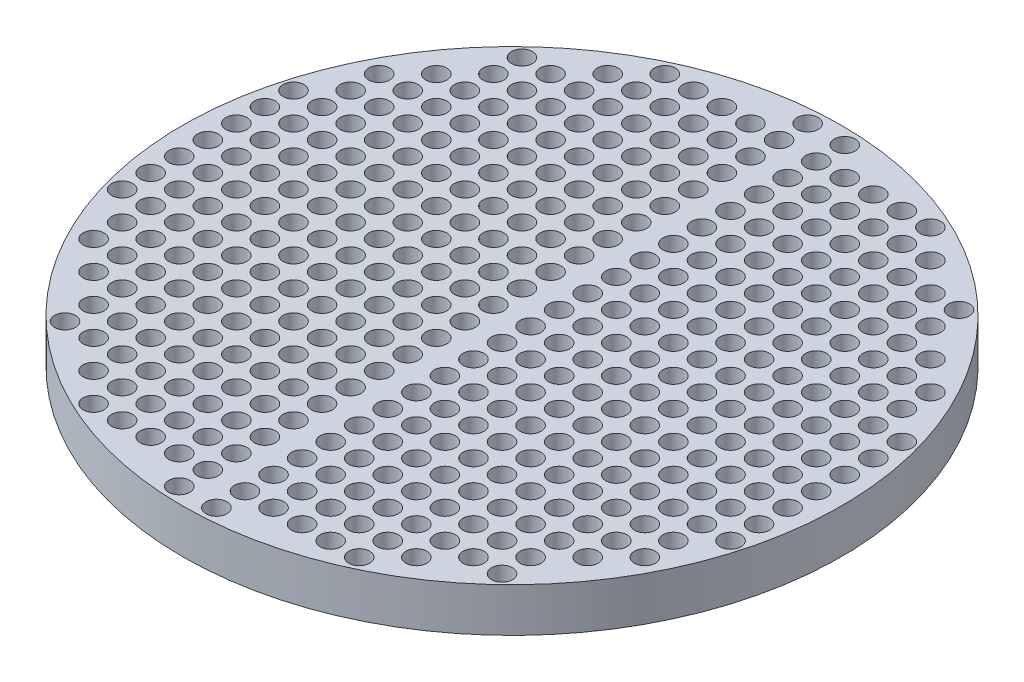
SolidWorks part; units mm, degrees
material " 12Х18Н10Т ГОСТ 4543-71"
ref_plane "Спереди" through (0, 0, 0) normal (0, 0, 1) x (1, 0, 0)
ref_plane "Сверху" through (0, 0, 0) normal (0, 1, 0) x (1, 0, 0)
ref_plane "Справа" through (0, 0, 0) normal (1, 0, 0) x (0, 0, -1)
sketch "Эскиз1" plane through (0, 0, 0) normal (0, 0, 1) x (1, 0, 0)
  line L0 (0, 0) -> (0, 152.1529) construction
  line L1 (-230, 35) -> (-259, 35)
  line L4 (-230, 35) -> (0, 35)
  line L5 (0, 35) -> (0, 75)
  line L7 (-300, 75) -> (-300, 35)
  line L8 (-300, 35) -> (-259, 35)
  line L11 (0, 75) -> (-300, 75)
  dimension "D1" = 600
  dimension "D2" = 40
revolve "Повернуть1" add sketch "Эскиз1" angle 360 about L0
ref_axis "Ось1" through (-80.9, 0, 0) along (1, 0, 0)
ref_axis "Ось2" through (0, 0, -80.9) along (0, 0, 1)
sketch "Sketch2" plane through (0, 75, 0) normal (0, 1, 0) x (1, 0, 0)
  line L0 (3.9158, 0) -> (298.9158, 0) construction
  line L2 (0, 0) -> (0, -73.9638) construction
  circle A1 centre (16.9158, 0) radius 9.525
  circle A2 centre (42.9158, 0) radius 9.525
  circle A3 centre (68.9158, 0) radius 9.525
  circle A4 centre (94.9158, 0) radius 9.525
  circle A5 centre (120.9158, 0) radius 9.525
  circle A6 centre (146.9158, 0) radius 9.525
  circle A7 centre (172.9158, 0) radius 9.525
  circle A8 centre (198.9158, 0) radius 9.525
  circle A9 centre (224.9158, 0) radius 9.525
  circle A10 centre (250.9158, 0) radius 9.525
  circle A11 centre (276.9158, 0) radius 9.525
  circle A12 centre (42.9158, 0) radius 9.525
  circle A13 centre (68.9158, 0) radius 9.525
  circle A14 centre (94.9158, 0) radius 9.525
  circle A15 centre (120.9158, 0) radius 9.525
  circle A16 centre (146.9158, 0) radius 9.525
  circle A17 centre (172.9158, 0) radius 9.525
  circle A18 centre (198.9158, 0) radius 9.525
  circle A19 centre (224.9158, 0) radius 9.525
  circle A20 centre (250.9158, 0) radius 9.525
  circle A21 centre (276.9158, 0) radius 9.525
  circle A22 centre (42.9158, 26) radius 9.525
  circle A23 centre (68.9158, 26) radius 9.525
  circle A24 centre (94.9158, 26) radius 9.525
  circle A25 centre (120.9158, 26) radius 9.525
  circle A26 centre (146.9158, 26) radius 9.525
  circle A27 centre (172.9158, 26) radius 9.525
  circle A28 centre (198.9158, 26) radius 9.525
  circle A29 centre (224.9158, 26) radius 9.525
  circle A30 centre (250.9158, 26) radius 9.525
  circle A31 centre (276.9158, 26) radius 9.525
  circle A32 centre (42.9158, 52) radius 9.525
  circle A33 centre (68.9158, 52) radius 9.525
  circle A34 centre (94.9158, 52) radius 9.525
  circle A35 centre (120.9158, 52) radius 9.525
  circle A36 centre (146.9158, 52) radius 9.525
  circle A37 centre (172.9158, 52) radius 9.525
  circle A38 centre (198.9158, 52) radius 9.525
  circle A39 centre (224.9158, 52) radius 9.525
  circle A40 centre (250.9158, 52) radius 9.525
  circle A41 centre (276.9158, 52) radius 9.525
  circle A42 centre (42.9158, 78) radius 9.525
  circle A43 centre (68.9158, 78) radius 9.525
  circle A44 centre (94.9158, 78) radius 9.525
  circle A45 centre (120.9158, 78) radius 9.525
  circle A46 centre (146.9158, 78) radius 9.525
  circle A47 centre (172.9158, 78) radius 9.525
  circle A48 centre (198.9158, 78) radius 9.525
  circle A49 centre (224.9158, 78) radius 9.525
  circle A50 centre (250.9158, 78) radius 9.525
  circle A51 centre (276.9158, 78) radius 9.525
  circle A52 centre (42.9158, 104) radius 9.525
  circle A53 centre (68.9158, 104) radius 9.525
  circle A54 centre (94.9158, 104) radius 9.525
  circle A55 centre (120.9158, 104) radius 9.525
  circle A56 centre (146.9158, 104) radius 9.525
  circle A57 centre (172.9158, 104) radius 9.525
  circle A58 centre (198.9158, 104) radius 9.525
  circle A59 centre (224.9158, 104) radius 9.525
  circle A60 centre (250.9158, 104) radius 9.525
  circle A61 centre (16.9158, -286) radius 9.525
  circle A62 centre (42.9158, 130) radius 9.525
  circle A63 centre (68.9158, 130) radius 9.525
  circle A64 centre (94.9158, 130) radius 9.525
  circle A65 centre (120.9158, 130) radius 9.525
  circle A66 centre (146.9158, 130) radius 9.525
  circle A67 centre (172.9158, 130) radius 9.525
  circle A68 centre (198.9158, 130) radius 9.525
  circle A69 centre (224.9158, 130) radius 9.525
  circle A70 centre (250.9158, 130) radius 9.525
  circle A71 centre (16.9158, -260) radius 9.525
  circle A72 centre (42.9158, 156) radius 9.525
  circle A73 centre (68.9158, 156) radius 9.525
  circle A74 centre (94.9158, 156) radius 9.525
  circle A75 centre (120.9158, 156) radius 9.525
  circle A76 centre (146.9158, 156) radius 9.525
  circle A77 centre (172.9158, 156) radius 9.525
  circle A78 centre (198.9158, 156) radius 9.525
  circle A79 centre (224.9158, 156) radius 9.525
  circle A80 centre (16.9158, -234) radius 9.525
  circle A81 centre (16.9158, -208) radius 9.525
  circle A82 centre (42.9158, 182) radius 9.525
  circle A83 centre (68.9158, 182) radius 9.525
  circle A84 centre (94.9158, 182) radius 9.525
  circle A85 centre (120.9158, 182) radius 9.525
  circle A86 centre (146.9158, 182) radius 9.525
  circle A87 centre (172.9158, 182) radius 9.525
  circle A88 centre (198.9158, 182) radius 9.525
  circle A89 centre (16.9158, -182) radius 9.525
  circle A90 centre (16.9158, -156) radius 9.525
  circle A91 centre (16.9158, -130) radius 9.525
  circle A92 centre (42.9158, 208) radius 9.525
  circle A93 centre (68.9158, 208) radius 9.525
  circle A94 centre (94.9158, 208) radius 9.525
  circle A95 centre (120.9158, 208) radius 9.525
  circle A96 centre (146.9158, 208) radius 9.525
  circle A97 centre (172.9158, 208) radius 9.525
  circle A98 centre (198.9158, 208) radius 9.525
  circle A99 centre (16.9158, -104) radius 9.525
  circle A100 centre (16.9158, -78) radius 9.525
  circle A101 centre (16.9158, -52) radius 9.525
  circle A102 centre (42.9158, 234) radius 9.525
  circle A103 centre (68.9158, 234) radius 9.525
  circle A104 centre (94.9158, 234) radius 9.525
  circle A105 centre (120.9158, 234) radius 9.525
  circle A106 centre (146.9158, 234) radius 9.525
  circle A107 centre (16.9158, -26) radius 9.525
  circle A108 centre (120.9158, -260) radius 9.525
  circle A109 centre (94.9158, -260) radius 9.525
  circle A110 centre (68.9158, -260) radius 9.525
  circle A111 centre (42.9158, -260) radius 9.525
  circle A112 centre (42.9158, 260) radius 9.525
  circle A113 centre (68.9158, 260) radius 9.525
  circle A114 centre (94.9158, 260) radius 9.525
  circle A115 centre (120.9158, 260) radius 9.525
  circle A116 centre (146.9158, -234) radius 9.525
  circle A117 centre (120.9158, -234) radius 9.525
  circle A118 centre (94.9158, -234) radius 9.525
  circle A119 centre (68.9158, -234) radius 9.525
  circle A120 centre (42.9158, -234) radius 9.525
  circle A121 centre (198.9158, -208) radius 9.525
  circle A122 centre (172.9158, -208) radius 9.525
  circle A123 centre (146.9158, -208) radius 9.525
  circle A124 centre (120.9158, -208) radius 9.525
  circle A125 centre (94.9158, -208) radius 9.525
  circle A126 centre (68.9158, -208) radius 9.525
  circle A127 centre (42.9158, -208) radius 9.525
  circle A128 centre (198.9158, -182) radius 9.525
  circle A129 centre (172.9158, -182) radius 9.525
  circle A130 centre (146.9158, -182) radius 9.525
  circle A131 centre (120.9158, -182) radius 9.525
  circle A132 centre (16.9158, 26) radius 9.525
  circle A133 centre (16.9158, 52) radius 9.525
  circle A134 centre (16.9158, 78) radius 9.525
  circle A135 centre (16.9158, 104) radius 9.525
  circle A136 centre (16.9158, 130) radius 9.525
  circle A137 centre (16.9158, 156) radius 9.525
  circle A138 centre (16.9158, 182) radius 9.525
  circle A139 centre (16.9158, 208) radius 9.525
  circle A140 centre (16.9158, 234) radius 9.525
  circle A141 centre (16.9158, 260) radius 9.525
  circle A142 centre (16.9158, 286) radius 9.525
  circle A143 centre (198.9158, 234) radius 9.525 [skipped]
  circle A144 centre (224.9158, 234) radius 9.525 [skipped]
  circle A145 centre (250.9158, 234) radius 9.525 [skipped]
  circle A146 centre (276.9158, 234) radius 9.525 [skipped]
  circle A147 centre (198.9158, 260) radius 9.525 [skipped]
  circle A148 centre (224.9158, 260) radius 9.525 [skipped]
  circle A149 centre (250.9158, 260) radius 9.525 [skipped]
  circle A150 centre (276.9158, 260) radius 9.525 [skipped]
  circle A151 centre (198.9158, 286) radius 9.525 [skipped]
  circle A152 centre (224.9158, 286) radius 9.525 [skipped]
  circle A153 centre (250.9158, 286) radius 9.525 [skipped]
  circle A154 centre (276.9158, 286) radius 9.525 [skipped]
  circle A155 centre (120.9158, 286) radius 9.525 [skipped]
  circle A156 centre (146.9158, 286) radius 9.525 [skipped]
  circle A157 centre (172.9158, 286) radius 9.525 [skipped]
  circle A158 centre (146.9158, 260) radius 9.525 [skipped]
  circle A159 centre (172.9158, 260) radius 9.525 [skipped]
  circle A160 centre (94.9158, 286) radius 9.525 [skipped]
  circle A161 centre (250.9158, 182) radius 9.525 [skipped]
  circle A162 centre (276.9158, 182) radius 9.525 [skipped]
  circle A163 centre (250.9158, 208) radius 9.525 [skipped]
  circle A164 centre (276.9158, 208) radius 9.525 [skipped]
  circle A165 centre (224.9158, 208) radius 9.525 [skipped]
  circle A166 centre (250.9158, 156) radius 9.525 [skipped]
  circle A167 centre (276.9158, 156) radius 9.525 [skipped]
  circle A168 centre (276.9158, 130) radius 9.525 [skipped]
  circle A169 centre (276.9158, 104) radius 9.525 [skipped]
  circle A170 centre (68.9158, 286) radius 9.525 [skipped]
  circle A171 centre (172.9158, 234) radius 9.525 [skipped]
  circle A172 centre (42.9158, 286) radius 9.525 [skipped]
  circle A173 centre (224.9158, 182) radius 9.525 [skipped]
  circle A174 centre (94.9158, -182) radius 9.525
  circle A175 centre (68.9158, -182) radius 9.525
  circle A176 centre (42.9158, -182) radius 9.525
  circle A177 centre (224.9158, -156) radius 9.525
  circle A178 centre (198.9158, -156) radius 9.525
  circle A179 centre (172.9158, -156) radius 9.525
  circle A180 centre (146.9158, -156) radius 9.525
  circle A181 centre (120.9158, -156) radius 9.525
  circle A182 centre (94.9158, -156) radius 9.525
  circle A183 centre (68.9158, -156) radius 9.525
  circle A184 centre (42.9158, -156) radius 9.525
  circle A185 centre (250.9158, -130) radius 9.525
  circle A186 centre (224.9158, -130) radius 9.525
  circle A187 centre (198.9158, -130) radius 9.525
  circle A188 centre (172.9158, -130) radius 9.525
  circle A189 centre (146.9158, -130) radius 9.525
  circle A190 centre (120.9158, -130) radius 9.525
  circle A191 centre (94.9158, -130) radius 9.525
  circle A192 centre (68.9158, -130) radius 9.525
  circle A193 centre (42.9158, -130) radius 9.525
  circle A194 centre (250.9158, -104) radius 9.525
  circle A195 centre (224.9158, -104) radius 9.525
  circle A196 centre (198.9158, -104) radius 9.525
  circle A197 centre (172.9158, -104) radius 9.525
  circle A198 centre (146.9158, -104) radius 9.525
  circle A199 centre (120.9158, -104) radius 9.525
  circle A200 centre (94.9158, -104) radius 9.525
  circle A201 centre (68.9158, -104) radius 9.525
  circle A202 centre (42.9158, -104) radius 9.525
  circle A203 centre (276.9158, -78) radius 9.525
  circle A204 centre (250.9158, -78) radius 9.525
  circle A205 centre (224.9158, -78) radius 9.525
  circle A206 centre (198.9158, -78) radius 9.525
  circle A207 centre (172.9158, -78) radius 9.525
  circle A208 centre (146.9158, -78) radius 9.525
  circle A209 centre (120.9158, -78) radius 9.525
  circle A210 centre (94.9158, -78) radius 9.525
  circle A211 centre (68.9158, -78) radius 9.525
  circle A212 centre (42.9158, -78) radius 9.525
  circle A213 centre (276.9158, -52) radius 9.525
  circle A214 centre (250.9158, -52) radius 9.525
  circle A215 centre (224.9158, -52) radius 9.525
  circle A216 centre (198.9158, -52) radius 9.525
  circle A217 centre (172.9158, -52) radius 9.525
  circle A218 centre (146.9158, -52) radius 9.525
  circle A219 centre (120.9158, -52) radius 9.525
  circle A220 centre (94.9158, -52) radius 9.525
  circle A221 centre (68.9158, -52) radius 9.525
  circle A222 centre (42.9158, -52) radius 9.525
  circle A223 centre (276.9158, -26) radius 9.525
  circle A224 centre (250.9158, -26) radius 9.525
  circle A225 centre (224.9158, -26) radius 9.525
  circle A226 centre (198.9158, -26) radius 9.525
  circle A227 centre (172.9158, -26) radius 9.525
  circle A228 centre (146.9158, -26) radius 9.525
  circle A229 centre (120.9158, -26) radius 9.525
  circle A230 centre (94.9158, -26) radius 9.525
  circle A231 centre (68.9158, -26) radius 9.525
  circle A232 centre (42.9158, -26) radius 9.525
  circle A233 centre (-42.9158, -26) radius 9.525
  circle A234 centre (-68.9158, -26) radius 9.525
  circle A235 centre (-94.9158, -26) radius 9.525
  circle A236 centre (-120.9158, -26) radius 9.525
  circle A237 centre (-146.9158, -26) radius 9.525
  circle A238 centre (-172.9158, -26) radius 9.525
  circle A239 centre (-198.9158, -26) radius 9.525
  circle A240 centre (-224.9158, -26) radius 9.525
  circle A241 centre (-250.9158, -26) radius 9.525
  circle A242 centre (-276.9158, -26) radius 9.525
  circle A243 centre (-42.9158, -52) radius 9.525
  circle A244 centre (-68.9158, -52) radius 9.525
  circle A245 centre (-94.9158, -52) radius 9.525
  circle A246 centre (-120.9158, -52) radius 9.525
  circle A247 centre (-146.9158, -52) radius 9.525
  circle A248 centre (-172.9158, -52) radius 9.525
  circle A249 centre (-198.9158, -52) radius 9.525
  circle A250 centre (-224.9158, -52) radius 9.525
  circle A251 centre (-250.9158, -52) radius 9.525
  circle A252 centre (-276.9158, -52) radius 9.525
  circle A253 centre (-42.9158, -78) radius 9.525
  circle A254 centre (-68.9158, -78) radius 9.525
  circle A255 centre (-94.9158, -78) radius 9.525
  circle A256 centre (-120.9158, -78) radius 9.525
  circle A257 centre (-146.9158, -78) radius 9.525
  circle A258 centre (-172.9158, -78) radius 9.525
  circle A259 centre (-198.9158, -78) radius 9.525
  circle A260 centre (-224.9158, -78) radius 9.525
  circle A261 centre (-250.9158, -78) radius 9.525
  circle A262 centre (-276.9158, -78) radius 9.525
  circle A263 centre (-42.9158, -104) radius 9.525
  circle A264 centre (-68.9158, -104) radius 9.525
  circle A265 centre (-94.9158, -104) radius 9.525
  circle A266 centre (-120.9158, -104) radius 9.525
  circle A267 centre (-146.9158, -104) radius 9.525
  circle A268 centre (-172.9158, -104) radius 9.525
  circle A269 centre (-198.9158, -104) radius 9.525
  circle A270 centre (-224.9158, -104) radius 9.525
  circle A271 centre (-250.9158, -104) radius 9.525
  circle A272 centre (-42.9158, -130) radius 9.525
  circle A273 centre (-68.9158, -130) radius 9.525
  circle A274 centre (-94.9158, -130) radius 9.525
  circle A275 centre (-120.9158, -130) radius 9.525
  circle A276 centre (-146.9158, -130) radius 9.525
  circle A277 centre (-172.9158, -130) radius 9.525
  circle A278 centre (-198.9158, -130) radius 9.525
  circle A279 centre (-224.9158, -130) radius 9.525
  circle A280 centre (-250.9158, -130) radius 9.525
  circle A281 centre (-42.9158, -156) radius 9.525
  circle A282 centre (-68.9158, -156) radius 9.525
  circle A283 centre (-94.9158, -156) radius 9.525
  circle A284 centre (-120.9158, -156) radius 9.525
  circle A285 centre (-146.9158, -156) radius 9.525
  circle A286 centre (-172.9158, -156) radius 9.525
  circle A287 centre (-198.9158, -156) radius 9.525
  circle A288 centre (-224.9158, -156) radius 9.525
  circle A289 centre (-42.9158, -182) radius 9.525
  circle A290 centre (-68.9158, -182) radius 9.525
  circle A291 centre (-94.9158, -182) radius 9.525
  circle A292 centre (-16.9158, 286) radius 9.525
  circle A293 centre (-16.9158, 260) radius 9.525
  circle A294 centre (-16.9158, 234) radius 9.525
  circle A295 centre (-16.9158, 208) radius 9.525
  circle A296 centre (-16.9158, 182) radius 9.525
  circle A297 centre (-16.9158, 156) radius 9.525
  circle A298 centre (-16.9158, 130) radius 9.525
  circle A299 centre (-16.9158, 104) radius 9.525
  circle A300 centre (-16.9158, 78) radius 9.525
  circle A301 centre (-16.9158, 52) radius 9.525
  circle A302 centre (-16.9158, 26) radius 9.525
  circle A303 centre (-120.9158, -182) radius 9.525
  circle A304 centre (-146.9158, -182) radius 9.525
  circle A305 centre (-172.9158, -182) radius 9.525
  circle A306 centre (-198.9158, -182) radius 9.525
  circle A307 centre (-42.9158, -208) radius 9.525
  circle A308 centre (-68.9158, -208) radius 9.525
  circle A309 centre (-94.9158, -208) radius 9.525
  circle A310 centre (-120.9158, -208) radius 9.525
  circle A311 centre (-146.9158, -208) radius 9.525
  circle A312 centre (-172.9158, -208) radius 9.525
  circle A313 centre (-198.9158, -208) radius 9.525
  circle A314 centre (-42.9158, -234) radius 9.525
  circle A315 centre (-68.9158, -234) radius 9.525
  circle A316 centre (-94.9158, -234) radius 9.525
  circle A317 centre (-120.9158, -234) radius 9.525
  circle A318 centre (-146.9158, -234) radius 9.525
  circle A319 centre (-120.9158, 260) radius 9.525
  circle A320 centre (-94.9158, 260) radius 9.525
  circle A321 centre (-68.9158, 260) radius 9.525
  circle A322 centre (-42.9158, 260) radius 9.525
  circle A323 centre (-42.9158, -260) radius 9.525
  circle A324 centre (-68.9158, -260) radius 9.525
  circle A325 centre (-94.9158, -260) radius 9.525
  circle A326 centre (-120.9158, -260) radius 9.525
  circle A327 centre (-16.9158, -26) radius 9.525
  circle A328 centre (-146.9158, 234) radius 9.525
  circle A329 centre (-120.9158, 234) radius 9.525
  circle A330 centre (-94.9158, 234) radius 9.525
  circle A331 centre (-68.9158, 234) radius 9.525
  circle A332 centre (-42.9158, 234) radius 9.525
  circle A333 centre (-16.9158, -52) radius 9.525
  circle A334 centre (-16.9158, -78) radius 9.525
  circle A335 centre (-16.9158, -104) radius 9.525
  circle A336 centre (-198.9158, 208) radius 9.525
  circle A337 centre (-172.9158, 208) radius 9.525
  circle A338 centre (-146.9158, 208) radius 9.525
  circle A339 centre (-120.9158, 208) radius 9.525
  circle A340 centre (-94.9158, 208) radius 9.525
  circle A341 centre (-68.9158, 208) radius 9.525
  circle A342 centre (-42.9158, 208) radius 9.525
  circle A343 centre (-16.9158, -130) radius 9.525
  circle A344 centre (-16.9158, -156) radius 9.525
  circle A345 centre (-16.9158, -182) radius 9.525
  circle A346 centre (-198.9158, 182) radius 9.525
  circle A347 centre (-172.9158, 182) radius 9.525
  circle A348 centre (-146.9158, 182) radius 9.525
  circle A349 centre (-120.9158, 182) radius 9.525
  circle A350 centre (-94.9158, 182) radius 9.525
  circle A351 centre (-68.9158, 182) radius 9.525
  circle A352 centre (-42.9158, 182) radius 9.525
  circle A353 centre (-16.9158, -208) radius 9.525
  circle A354 centre (-16.9158, -234) radius 9.525
  circle A355 centre (-224.9158, 156) radius 9.525
  circle A356 centre (-198.9158, 156) radius 9.525
  circle A357 centre (-172.9158, 156) radius 9.525
  circle A358 centre (-146.9158, 156) radius 9.525
  circle A359 centre (-120.9158, 156) radius 9.525
  circle A360 centre (-94.9158, 156) radius 9.525
  circle A361 centre (-68.9158, 156) radius 9.525
  circle A362 centre (-42.9158, 156) radius 9.525
  circle A363 centre (-16.9158, -260) radius 9.525
  circle A364 centre (-250.9158, 130) radius 9.525
  circle A365 centre (-224.9158, 130) radius 9.525
  circle A366 centre (-198.9158, 130) radius 9.525
  circle A367 centre (-172.9158, 130) radius 9.525
  circle A368 centre (-146.9158, 130) radius 9.525
  circle A369 centre (-120.9158, 130) radius 9.525
  circle A370 centre (-94.9158, 130) radius 9.525
  circle A371 centre (-68.9158, 130) radius 9.525
  circle A372 centre (-42.9158, 130) radius 9.525
  circle A373 centre (-16.9158, -286) radius 9.525
  circle A374 centre (-250.9158, 104) radius 9.525
  circle A375 centre (-224.9158, 104) radius 9.525
  circle A376 centre (-198.9158, 104) radius 9.525
  circle A377 centre (-172.9158, 104) radius 9.525
  circle A378 centre (-146.9158, 104) radius 9.525
  circle A379 centre (-120.9158, 104) radius 9.525
  circle A380 centre (-94.9158, 104) radius 9.525
  circle A381 centre (-68.9158, 104) radius 9.525
  circle A382 centre (-42.9158, 104) radius 9.525
  circle A383 centre (-276.9158, 78) radius 9.525
  circle A384 centre (-250.9158, 78) radius 9.525
  circle A385 centre (-224.9158, 78) radius 9.525
  circle A386 centre (-198.9158, 78) radius 9.525
  circle A387 centre (-172.9158, 78) radius 9.525
  circle A388 centre (-146.9158, 78) radius 9.525
  circle A389 centre (-120.9158, 78) radius 9.525
  circle A390 centre (-94.9158, 78) radius 9.525
  circle A391 centre (-68.9158, 78) radius 9.525
  circle A392 centre (-42.9158, 78) radius 9.525
  circle A393 centre (-276.9158, 52) radius 9.525
  circle A394 centre (-250.9158, 52) radius 9.525
  circle A395 centre (-224.9158, 52) radius 9.525
  circle A396 centre (-198.9158, 52) radius 9.525
  circle A397 centre (-172.9158, 52) radius 9.525
  circle A398 centre (-146.9158, 52) radius 9.525
  circle A399 centre (-120.9158, 52) radius 9.525
  circle A400 centre (-94.9158, 52) radius 9.525
  circle A401 centre (-68.9158, 52) radius 9.525
  circle A402 centre (-42.9158, 52) radius 9.525
  circle A403 centre (-276.9158, 26) radius 9.525
  circle A404 centre (-250.9158, 26) radius 9.525
  circle A405 centre (-224.9158, 26) radius 9.525
  circle A406 centre (-198.9158, 26) radius 9.525
  circle A407 centre (-172.9158, 26) radius 9.525
  circle A408 centre (-146.9158, 26) radius 9.525
  circle A409 centre (-120.9158, 26) radius 9.525
  circle A410 centre (-94.9158, 26) radius 9.525
  circle A411 centre (-68.9158, 26) radius 9.525
  circle A412 centre (-42.9158, 26) radius 9.525
  circle A413 centre (-276.9158, 0) radius 9.525
  circle A414 centre (-250.9158, 0) radius 9.525
  circle A415 centre (-224.9158, 0) radius 9.525
  circle A416 centre (-198.9158, 0) radius 9.525
  circle A417 centre (-172.9158, 0) radius 9.525
  circle A418 centre (-146.9158, 0) radius 9.525
  circle A419 centre (-120.9158, 0) radius 9.525
  circle A420 centre (-94.9158, 0) radius 9.525
  circle A421 centre (-68.9158, 0) radius 9.525
  circle A422 centre (-42.9158, 0) radius 9.525
  circle A423 centre (-276.9158, 0) radius 9.525
  circle A424 centre (-250.9158, 0) radius 9.525
  circle A425 centre (-224.9158, 0) radius 9.525
  circle A426 centre (-198.9158, 0) radius 9.525
  circle A427 centre (-172.9158, 0) radius 9.525
  circle A428 centre (-146.9158, 0) radius 9.525
  circle A429 centre (-120.9158, 0) radius 9.525
  circle A430 centre (-94.9158, 0) radius 9.525
  circle A431 centre (-68.9158, 0) radius 9.525
  circle A432 centre (-42.9158, 0) radius 9.525
  circle A433 centre (-16.9158, 0) radius 9.525
  dimension "D2" = 11
  dimension "D3" = 11
  dimension "D4" = 12
extrude "Cut-Extrude1" cut sketch "Sketch2" against normal through all
